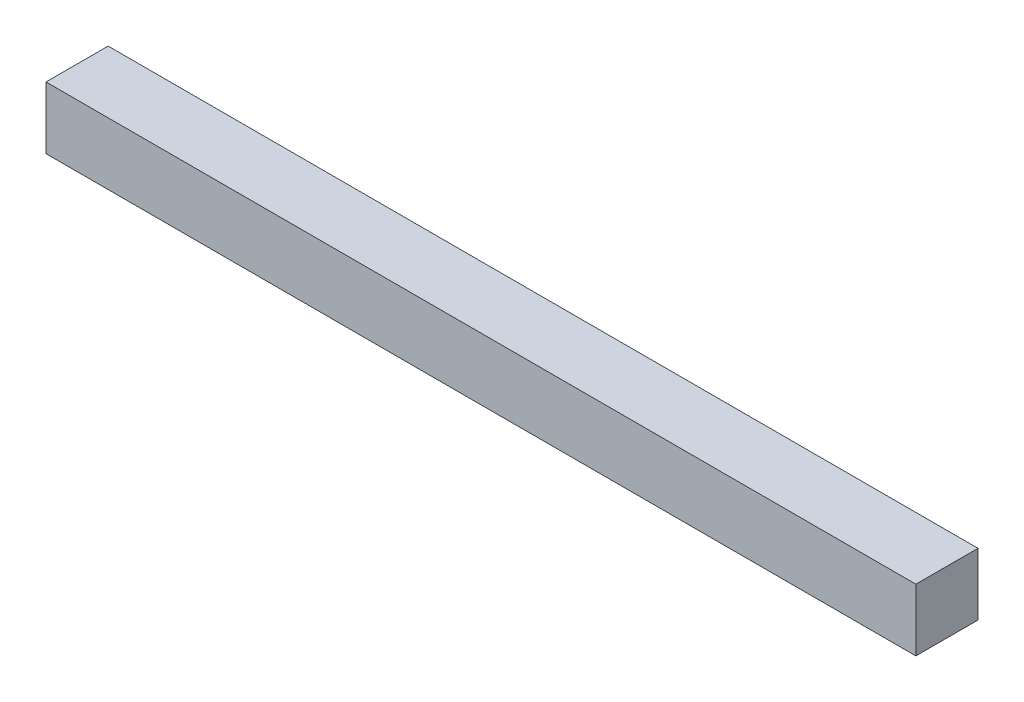
SolidWorks part; units mm, degrees
ref_plane "Front Plane" through (0, 0, 0) normal (0, 0, 1) x (1, 0, 0)
ref_plane "Top Plane" through (0, 0, 0) normal (0, 1, 0) x (1, 0, 0)
ref_plane "Right Plane" through (0, 0, 0) normal (1, 0, 0) x (0, 0, -1)
sketch "Sketch1" plane through (0, 0, 0) normal (1, 0, 0) x (0, 0, -1)
  line L1 (-9.525, -9.525) -> (9.525, -9.525)
  line L2 (-9.525, -9.525) -> (-9.525, 9.525)
  line L3 (-9.525, 9.525) -> (9.525, 9.525)
  line L4 (9.525, -9.525) -> (9.525, 9.525)
  line L5 (-9.525, -9.525) -> (9.525, 9.525) construction
  line L6 (-9.525, 9.525) -> (9.525, -9.525) construction
  point P0 (0, 0)
  dimension "D1" = 19.05
  dimension "D2" = 19.05
extrude "Boss-Extrude1" add sketch "Sketch1" along normal mid plane 266.7
sketch "Sketch2" [suppressed] plane through (0, 0, 0) normal (1, 0, 0) x (0, 0, -1)
  line L0 (-9.525, 9.525) -> (9.525, -9.525)
  line L1 (31.75, 9.525) -> (-31.75, 9.525) construction
  line L2 (-31.75, -9.525) -> (31.75, -9.525) construction
  dimension "D1" = 45
extrude "Cut-Extrude1" [suppressed] cut sketch "Sketch2" against normal through all and the other way through all flip side to cut
